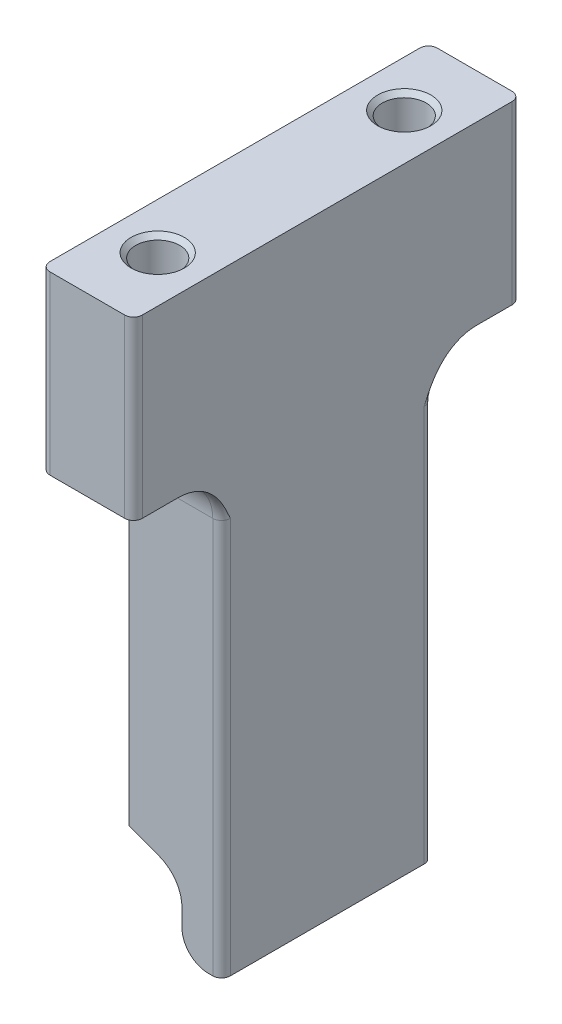
SolidWorks part; units mm, degrees
material "K110"
ref_plane "Front Plane" through (0, 0, 0) normal (0, 0, 1) x (1, 0, 0)
ref_plane "Top Plane" through (0, 0, 0) normal (0, 1, 0) x (1, 0, 0)
ref_plane "Right Plane" through (0, 0, 0) normal (1, 0, 0) x (0, 0, -1)
sketch "Sketch1" plane through (0, 0, 0) normal (0, 1, 0) x (1, 0, 0)
  line L1 (-5.25, -12) -> (5.25, -12)
  line L2 (-5.25, -12) -> (-5.25, 12)
  line L3 (-5.25, 12) -> (5.25, 12)
  line L4 (5.25, -12) -> (5.25, 12)
  line L5 (-5.25, -12) -> (5.25, 12) construction
  line L6 (-5.25, 12) -> (5.25, -12) construction
  point P0 (0, 0)
  dimension "D1" = 10.5
  dimension "D2" = 24
extrude "Boss-Extrude1" add sketch "Sketch1" against normal blind 70
sketch "Sketch2" plane through (0, 0, 12) normal (0, 0, 1) x (1, 0, 0)
  line L0 (-5.25, 0) -> (5.25, 0) construction
  line L1 (-5.25, -70) -> (0.75, -70) construction
  line L2 (-5.25, -70) -> (-5.25, -61) construction
  line L3 (-5.25, -61) -> (-3.25, -61) construction
  line L4 (0.75, -70) -> (0.75, -65) construction
  line L5 (5.25, -70) -> (5.25, 0) construction
  line L6 (-1.8819, -61.2412) -> (-5.25, -60.0153)
  line L7 (-5.25, -70) -> (-5.25, 0) construction
  line L8 (0.75, -65) -> (0.75, -70)
  line L9 (0.75, -70) -> (-5.25, -70)
  line L10 (-5.25, -70) -> (-5.25, -60.0153)
  arc A0 (-3.25, -61) -> (0.75, -65) centre (-3.25, -65) cw construction
  arc A1 (0.75, -65) -> (-1.8819, -61.2412) centre (-3.25, -65) ccw
  dimension "D3" = 4
  dimension "D1" = 61
  dimension "D2" = 4.5
  dimension "D4" = 2
  dimension "D5" = 20
extrude "Cut-Extrude1" cut sketch "Sketch2" against normal up to next
fillet "Fillet1" radius 3 1 edges at (0.75, -70, 0)
sketch "Sketch3" plane through (0, 0, 0) normal (0, 1, 0) x (1, 0, 0)
  line L0 (5.25, -12) -> (5.25, 12) construction
  line L1 (-5.25, -22) -> (5.25, -22)
  line L2 (-5.25, -22) -> (-5.25, 22)
  line L3 (-5.25, 22) -> (5.25, 22)
  line L4 (5.25, -22) -> (5.25, 22)
  line L5 (-5.25, 12) -> (-5.25, -12) construction
  line L6 (-5.25, 0) -> (5.25, 0) construction
  line L7 (-5.25, -12) -> (5.25, -12) construction
  dimension "D1" = 10
extrude "Boss-Extrude2" add sketch "Sketch3" against normal blind 20
fillet "Fillet2" radius 1 2 edges at (5.25, -45, -12) (5.25, -45, 12)
hole_wizard "M6 Tapped Hole1" positions "Sketch6" profile "Sketch5" tap size "M6" standard "ISO"
sketch "Sketch6" plane through (0, 0, 0) normal (0, 1, 0) x (1, 0, 0)
  line L0 (-5.25, -22) -> (5.25, -22) construction
  line L1 (5.25, 22) -> (-5.25, 22) construction
  point P0 (0, 14)
  point P2 (0, -14)
  dimension "D1" = 8
  dimension "D2" = 8
sketch "Sketch5" plane through (0, 0, -14) normal (1, 0, 0) x (0, 0, 1)
  line L0 (0, 0) -> (0, 18.5022)
  line L1 (0, 18.5022) -> (2.5, 17)
  line L2 (2.5, 17) -> (2.5, 0.525)
  line L3 (2.5, 0.525) -> (3.025, 0)
  line L5 (3.025, 0) -> (0, 0)
  line L6 (-2.5, 0.525) -> (-3.025, 0) construction
  line L10 (0, 18.5022) -> (-2.5, 17) construction
  line L11 (0, -6.35) -> (0, 107.95) construction
  dimension "Tap Drill Dia." = 5
  dimension "Tap Drill Depth" = 17
  dimension "Near C'Sink Dia." = 6.05
  dimension "Near C'Sink Angle" = 90
  dimension "Drill Angle" = 118
cosmetic thread "Hole Thread1" parameters "D1"=12, "D2"=6
cosmetic thread "Hole Thread2" parameters "D1"=12, "D2"=6
fillet "Fillet3" radius 5 4 edges at (4.9571, -20, -11.7071) (4.9571, -20, 11.7071) (-0.5, -20, -12) (-0.5, -20, 12)
fillet "Fillet4" radius 1 4 edges at (-5.25, -10, -22) (5.25, -10, -22) (-5.25, -10, 22) (5.25, -10, 22)
ref_plane "Plane1" through (0, -50, 0) normal (0, 1, 0) x (1, 0, 0)
sketch "Sketch8" plane through (0, -50, 0) normal (0, 1, 0) x (1, 0, 0)
  line L0 (-5.25, 12) -> (-5.25, -12)
  line L1 (-5.25, 12) -> (-5.25, -12)
  line L2 (-5.25, -12) -> (4.25, -12)
  line L3 (-5.25, -12) -> (4.25, -12)
  line L4 (5.25, -11) -> (5.25, 11)
  line L5 (5.25, -11) -> (5.25, 11)
  line L6 (4.25, 12) -> (-5.25, 12)
  line L7 (4.25, 12) -> (-5.25, 12)
  arc A0 (4.25, -12) -> (5.25, -11) centre (4.25, -11) ccw
  arc A1 (4.25, -12) -> (5.25, -11) centre (4.25, -11) ccw
  arc A2 (5.25, 11) -> (4.25, 12) centre (4.25, 11) ccw
  arc A3 (5.25, 11) -> (4.25, 12) centre (4.25, 11) ccw
